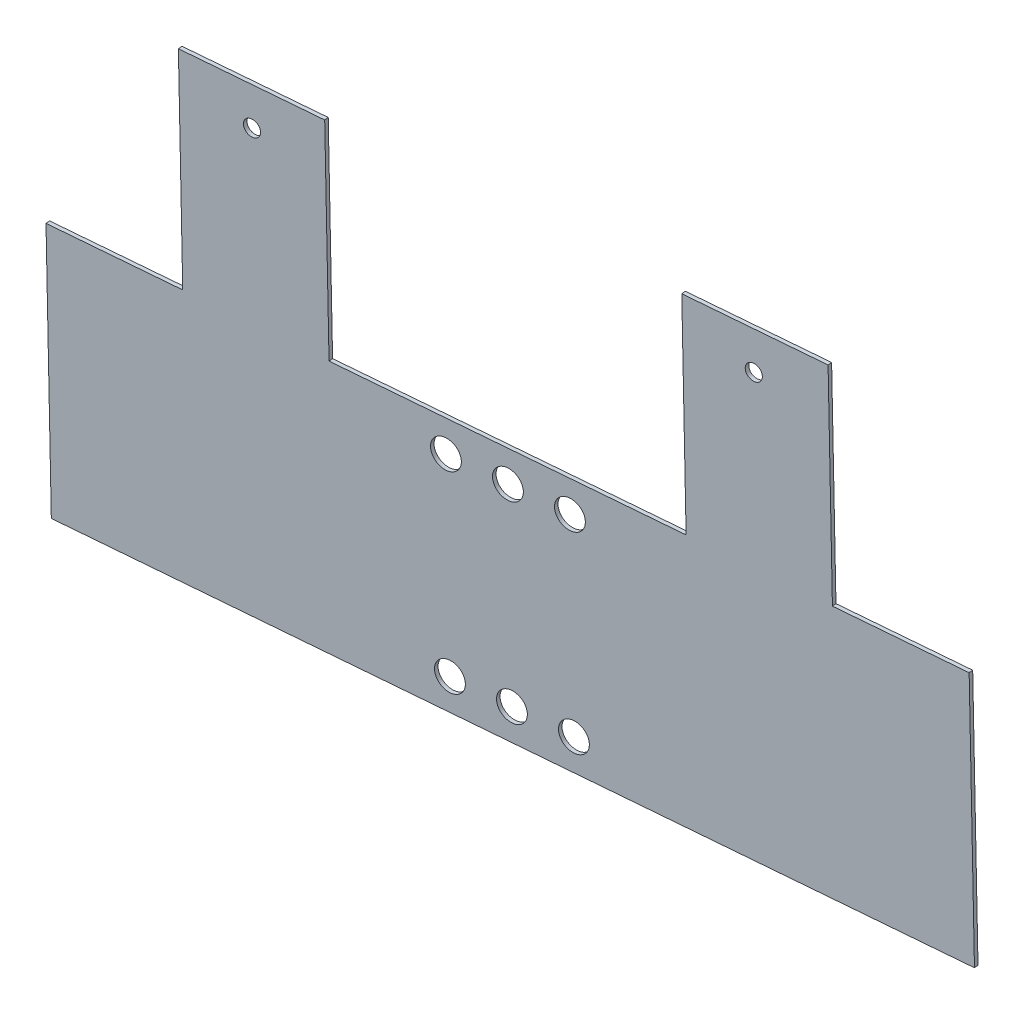
SolidWorks part; units mm, degrees
ref_plane "Front Plane" through (0, 0, 0) normal (0, 0, 1) x (1, 0, 0)
ref_plane "Top Plane" through (0, 0, 0) normal (0, 1, 0) x (1, 0, 0)
ref_plane "Right Plane" through (0, 0, 0) normal (1, 0, 0) x (0, 0, -1)
sketch "Sketch1" plane through (16.9972, -4.1499, 204.6314) normal (-0.0828, 0.0202, -0.9964) x (0.9966, 0.002, -0.0827)
  line L0 (-405.6316, 283.217) -> (-385.6926, 283.217)
  line L1 (-520.3126, 323.857) -> (-500.3736, 323.857)
  line L2 (-520.3126, 323.857) -> (-520.3126, 283.217)
  line L3 (-520.3126, 283.217) -> (-500.3736, 283.217)
  line L4 (-385.6926, 323.857) -> (-385.6926, 283.217)
  line L6 (-426.9676, 283.217) -> (-426.9676, 250.0037)
  line L7 (-426.9676, 250.0037) -> (-405.6316, 250.0037)
  line L8 (-405.6316, 283.217) -> (-405.6316, 250.0037)
  line L9 (-405.0144, 323.857) -> (-385.6926, 323.857)
  line L14 (-479.4985, 323.857) -> (-465.3599, 323.857)
  line L20 (-500.3736, 283.217) -> (-500.3736, 250.0037)
  line L21 (-500.3736, 250.0037) -> (-479.0376, 250.0037)
  line L22 (-479.0376, 283.217) -> (-479.0376, 250.0037)
  line L23 (-479.0376, 283.217) -> (-426.9676, 283.217)
  line L24 (-432.4144, 323.857) -> (-405.0144, 323.857)
  line L25 (-500.3736, 323.857) -> (-479.4985, 323.857)
  line L26 (-445.0971, 323.857) -> (-432.4144, 323.857)
  line L31 (-465.3599, 323.857) -> (-445.0971, 323.857)
  dimension "D1" = 134.62
  dimension "D2" = 40.64
  dimension "D3" = 21.336
  dimension "D4" = 52.07
  dimension "D5" = 33.2133
extrude "Boss-Extrude1" add sketch "Sketch1" along normal blind 0.6096
ref_plane "Plane1" through (-508.5923, -1, 42.2247) normal (0.9966, 0.002, -0.0827) x (-0.0828, 0.028, -0.9962)
sketch "Sketch5" plane through (16.9468, -4.1376, 204.024) normal (-0.0828, 0.0202, -0.9964) x (-0.9966, -0.0017, 0.0827)
  circle A0 centre (461.9962, -318.9871) radius 2.25
  circle A1 centre (452.9566, -318.9845) radius 2.25
  circle A2 centre (443.9171, -318.982) radius 2.25
  dimension "D1" = 4.5
extrude "Cut-Extrude2" cut sketch "Sketch5" against normal up to surface (0.6096 mm away) up to face at (-434.373, -283.8993, 236.4501)
ref_plane "Plane2" through (0.0852, -303.4744, -6.1615) normal (0.0003, -0.9998, -0.0203) x (-1, -0.0003, 0)
mirror "Mirror1" about plane through (0.0852, -303.4744, -6.1615) normal (0.0003, -0.9998, -0.0203) of "Cut-Extrude2"
sketch "Sketch6" plane through (16.9468, -4.1376, 204.024) normal (-0.0828, 0.0202, -0.9964) x (-0.9966, -0.0017, 0.0827)
  circle A1 centre (416.5068, -256.1738) radius 1.25
  dimension "D1" = 2.5
extrude "Cut-Extrude5" cut sketch "Sketch6" against normal up to surface (0.6096 mm away) up to face at (-445.6649, -293.213, 237.1991)
ref_plane "Plane3" through (-451.4485, -0.8877, 37.4805) normal (-0.9966, -0.002, 0.0827) x (0.0827, 0.0002, 0.9966)
sketch "Sketch7" plane through (16.9468, -4.1376, 204.024) normal (-0.0828, 0.0202, -0.9964) x (-0.9966, -0.0017, 0.0827)
  circle A0 centre (489.6815, -256.1944) radius 1.25
extrude "Cut-Extrude6" cut sketch "Sketch7" against normal up to surface (0.6096 mm away) up to face at (-399.3264, -260.97, 234.004)
